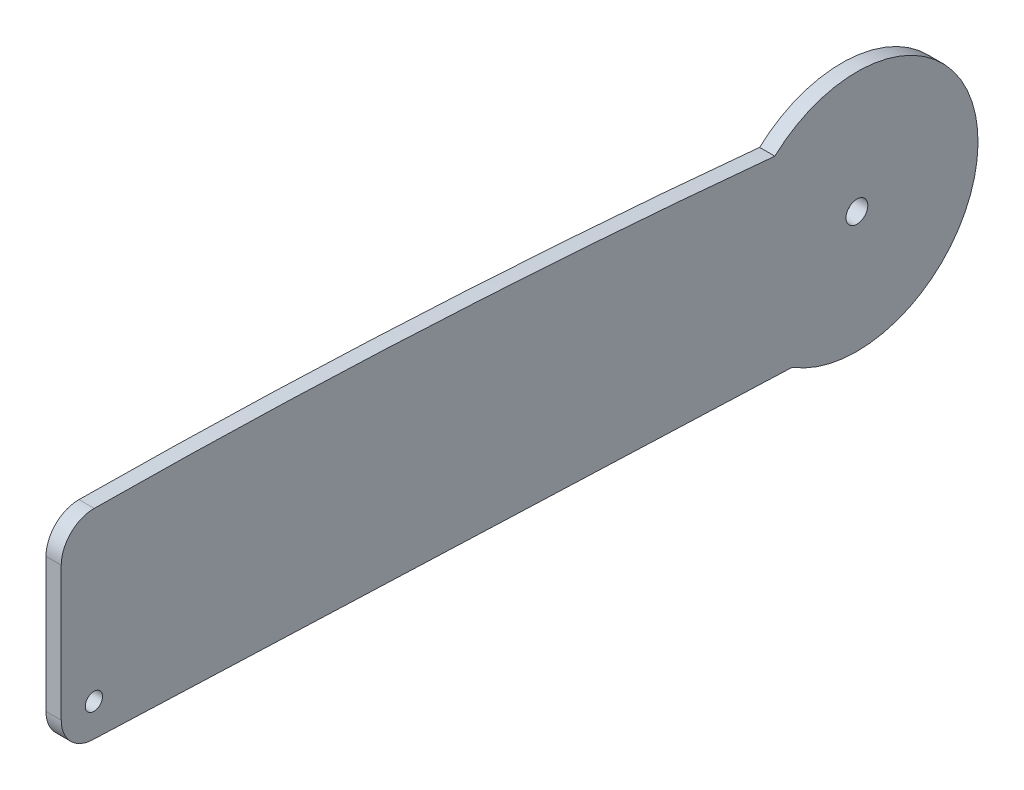
SolidWorks part; units mm, degrees
material "Beech"
ref_plane "Front" through (0, 0, 0) normal (0, 0, 1) x (1, 0, 0)
ref_plane "Top" through (0, 0, 0) normal (0, 1, 0) x (1, 0, 0)
ref_plane "Right" through (0, 0, 0) normal (1, 0, 0) x (0, 0, -1)
ref_axis "side-side" through (80.9, 0, 0) along (-1, 0, 0)
ref_axis "up-down" through (0, 50, 0) along (0, -1, 0)
ref_axis "front-back" through (0, 0, -80.9) along (0, 0, 1)
sketch "Sketch1" plane through (0, 0, 0) normal (1, 0, 0) x (0, 0, -1)
  line L10 (-364.4589, -24.3751) -> (-23.6778, -37.6187)
  line L15 (-535.345, -46.1379) -> (-441.6488, -92.9736)
  line L16 (-391.2831, -61.8422) -> (-391.2831, -41.4241)
  line L20 (-30.1249, 32.6847) -> (-392.4, 46.7636)
  line L151 (-405.9448, 45.5629) -> (-527.2317, 18.9913)
  circle A2 centre (0, 0) radius 11.5
  arc A12 (-527.2317, 18.9913) -> (-535.345, -46.1379) centre (-519.7834, -15.0065) ccw
  arc A13 (-441.6488, -92.9736) -> (-391.2831, -61.8422) centre (-426.0872, -61.8422) ccw
  arc A15 (-23.6778, -37.6187) -> (-30.1249, 32.6847) centre (0, 0) ccw
  arc A23 (-391.2831, -41.4241) -> (-364.4589, -24.3751) centre (-394.4803, -6.7672) ccw
  arc A268 (-392.4, 46.7636) -> (-405.9448, 45.5629) centre (-394.4803, -6.7672) ccw
sketch "Sketch3" plane through (0, 0, 0) normal (1, 0, 0) x (0, 0, -1)
  circle A2 centre (-426.0872, -61.8422) radius 2.3813
  circle A4 centre (-394.4803, -6.7672) radius 2.3813
  circle A6 centre (-457.7546, -1.4172) radius 2.3813
  circle A8 centre (-519.7834, -15.0065) radius 2.3812
  circle A92 centre (-474.5189, -58.6553) radius 1.7272
  circle A93 centre (-485.2525, -53.2899) radius 1.7272
  circle A94 centre (-385.7372, -50.1857) radius 1.7272
  circle A95 centre (-379.0063, -40.2511) radius 1.7272
  circle A96 centre (-498.7714, 29.9682) radius 1.7272
  circle A97 centre (-510.7706, 30.1019) radius 1.7272
  circle A98 centre (-359.2766, 19.9282) radius 1.7272
  circle A99 centre (-367.6668, 28.5075) radius 1.7272
sketch "Sketch4" plane through (0, 0, 0) normal (1, 0, 0) x (0, 0, -1)
  line L12 (-460.0851, -49.3735) -> (-460.8018, -59.3478)
  line L13 (-498.5693, -42.5979) -> (-463.7881, -45.0971)
  line L14 (-516.1804, 35.9104) -> (-543.504, 10.4623)
  line L15 (-367.5783, 36.4445) -> (-510.6822, 38.0389)
  line L16 (-371.1745, -41.5427) -> (-359.8351, 27.2159)
  line L17 (-397.2737, -81.3642) -> (-372.435, -44.7034)
  circle A1 centre (-367.6668, 28.5075) radius 1.905
  circle A3 centre (-510.7706, 30.1019) radius 1.905
  circle A5 centre (-379.0063, -40.2511) radius 1.905
  arc A12 (-460.8018, -59.3478) -> (-397.2737, -81.3642) centre (-426.0872, -61.8422) ccw
  arc A13 (-460.0851, -49.3735) -> (-463.7881, -45.0971) centre (-464.0748, -49.0868) ccw
  arc A14 (-543.504, 10.4623) -> (-498.5693, -42.5979) centre (-519.7834, -15.0065) ccw
  arc A15 (-510.6822, 38.0389) -> (-516.1804, 35.9104) centre (-510.7706, 30.1019) ccw
  arc A16 (-359.8351, 27.2159) -> (-367.5783, 36.4445) centre (-367.6668, 28.5075) ccw
  arc A17 (-372.435, -44.7034) -> (-371.1745, -41.5427) centre (-379.0063, -40.2511) ccw
sketch "Sketch2" plane through (0, 0, 0) normal (1, 0, 0) x (0, 0, -1)
  line L0 (0, 50) -> (0, -50) construction
  line L3 (-397.2737, -81.3642) -> (-372.435, -44.7034) construction
  line L4 (-292, 33.638) -> (-292, -15.6483)
  line L5 (-364.4589, -24.3751) -> (-23.6778, -37.6187) construction
  line L7 (-30.1249, 32.6847) -> (-503.0574, 37.954) construction
  line L16 (-379.1659, -54.6379) -> (-361.3036, -28.2739) construction
  line L17 (-354.3699, -24.7672) -> (-23.6778, -37.6187) construction
  line L18 (-23.6778, -37.6187) -> (-280.466, -27.6393)
  line L20 (-485.7375, -32.025) -> (-494.1451, -48.8447) construction
  line L22 (-490.5663, -59.5775) -> (-476.359, -66.6793) construction
  line L23 (-535.345, -46.1379) -> (-441.6488, -92.9736) construction
  line L24 (-465.6263, -63.1004) -> (-457.2186, -46.2806) construction
  circle A0 centre (-379.0063, -40.2511) radius 1.7272 construction
  arc A1 (-23.6778, -37.6187) -> (-30.1249, 32.6847) centre (0, 0) ccw construction
  circle A2 centre (-379.0063, -40.2511) radius 1.7272 construction
  arc A6 (-23.6778, -37.6187) -> (-30.1249, 32.6847) centre (0, 0) ccw
  circle A11 centre (0, 0) radius 4
  arc A13 (-391.9332, -55.1469) -> (-457.2186, -46.2806) centre (-426.0872, -61.8422) ccw construction
  arc A14 (-441.6488, -92.9736) -> (-391.2831, -61.8422) centre (-426.0872, -61.8422) ccw construction
  circle A15 centre (-367.6668, 28.5075) radius 1.7272 construction
  circle A17 centre (-510.7706, 30.1019) radius 1.7272 construction
  arc A19 (-510.6822, 38.0389) -> (-516.1804, 35.9104) centre (-510.7706, 30.1019) ccw construction
  arc A20 (-511.3546, 38.0179) -> (-512.3258, 22.3183) centre (-510.7706, 30.1019) ccw construction
  circle A24 centre (-359.2766, 19.9282) radius 1.7272 construction
  circle A25 centre (-457.7546, -1.4172) radius 2.2542 construction
  circle A26 centre (-394.4803, -6.7672) radius 2.2542 construction
  arc A28 (-362.7596, 34.7464) -> (-362.755, 34.7428) centre (-367.6668, 28.5075) ccw construction
  arc A29 (-391.9332, -55.1469) -> (-379.1659, -54.6379) centre (-385.7372, -50.1857) ccw construction
  arc A30 (-485.7375, -32.025) -> (-512.3258, 22.3183) centre (-519.7834, -15.0065) ccw construction
  arc A31 (-543.504, 10.4623) -> (-498.5693, -42.5979) centre (-519.7834, -15.0065) ccw construction
  circle A32 centre (-280, -15.6483) radius 3.175
  circle A33 centre (-367.6668, 28.5075) radius 1.7272 construction
  circle A34 centre (-359.2766, 19.9282) radius 1.7272 construction
  circle A35 centre (-385.7372, -50.1857) radius 1.7272 construction
  arc A36 (-448.0381, -34.8332) -> (-483.1223, -25.2398) centre (-457.7546, -1.4172) cw construction
  arc A37 (-354.3699, -24.7672) -> (-361.3036, -28.2739) centre (-354.6806, -32.7612) ccw construction
  circle A38 centre (-457.7546, -1.4172) radius 2.3813 construction
  circle A39 centre (-394.4803, -6.7672) radius 2.3813 construction
  circle A40 centre (-510.7706, 30.1019) radius 1.7272 construction
  circle A41 centre (-498.7714, 29.9682) radius 1.7272 construction
  circle A42 centre (-390.4197, 18.3061) radius 1.3526 construction
  circle A43 centre (-392.45, 5.7695) radius 1.3526 construction
  arc A44 (-476.359, -66.6793) -> (-465.6263, -63.1004) centre (-472.7821, -59.5235) ccw construction
  arc A45 (-494.1451, -48.8447) -> (-490.5663, -59.5775) centre (-486.9894, -52.4217) ccw construction
  circle A46 centre (-385.7372, -50.1857) radius 1.7272 construction
  circle A47 centre (-498.7714, 29.9682) radius 1.7272 construction
  circle A48 centre (-474.5189, -58.6553) radius 1.7272 construction
  circle A49 centre (-485.2525, -53.2899) radius 1.7272 construction
  circle A50 centre (-474.5189, -58.6553) radius 1.7272 construction
  circle A51 centre (-485.2525, -53.2899) radius 1.7272 construction
  arc A52 (-30.1249, 32.6847) -> (-511.3546, 38.0179) centre (-302.1394, -2797.9349) ccw construction
  arc A53 (-279.9062, 45.6377) -> (-30.1249, 32.6847) centre (-302.1394, -2797.9349) cw
  arc A56 (-292, 33.638) -> (-279.9062, 45.6377) centre (-280, 33.638) cw
  arc A57 (-292, -15.6483) -> (-280.466, -27.6393) centre (-280, -15.6483) ccw
  point P73 (-292, 45.7065)
  point P95 (-292, -27.1911)
  dimension "D1" = 34.8
  dimension "D2" = 8
  dimension "D3" = 4.5085
  dimension "D4" = 8
  dimension "D5" = 8
  dimension "D6" = 15.875
  dimension "D7" = 61.0608
  dimension "D8" = 6.35
  dimension "D12" = 12
  dimension "D13" = 12
  dimension "D14" = 12
  dimension "D15" = 8
  dimension "D9" = 70
  dimension "D10" = 280
  dimension "D11" = 12
extrude "Boss-Extrude1" add sketch "Sketch2" along normal blind 5.588
